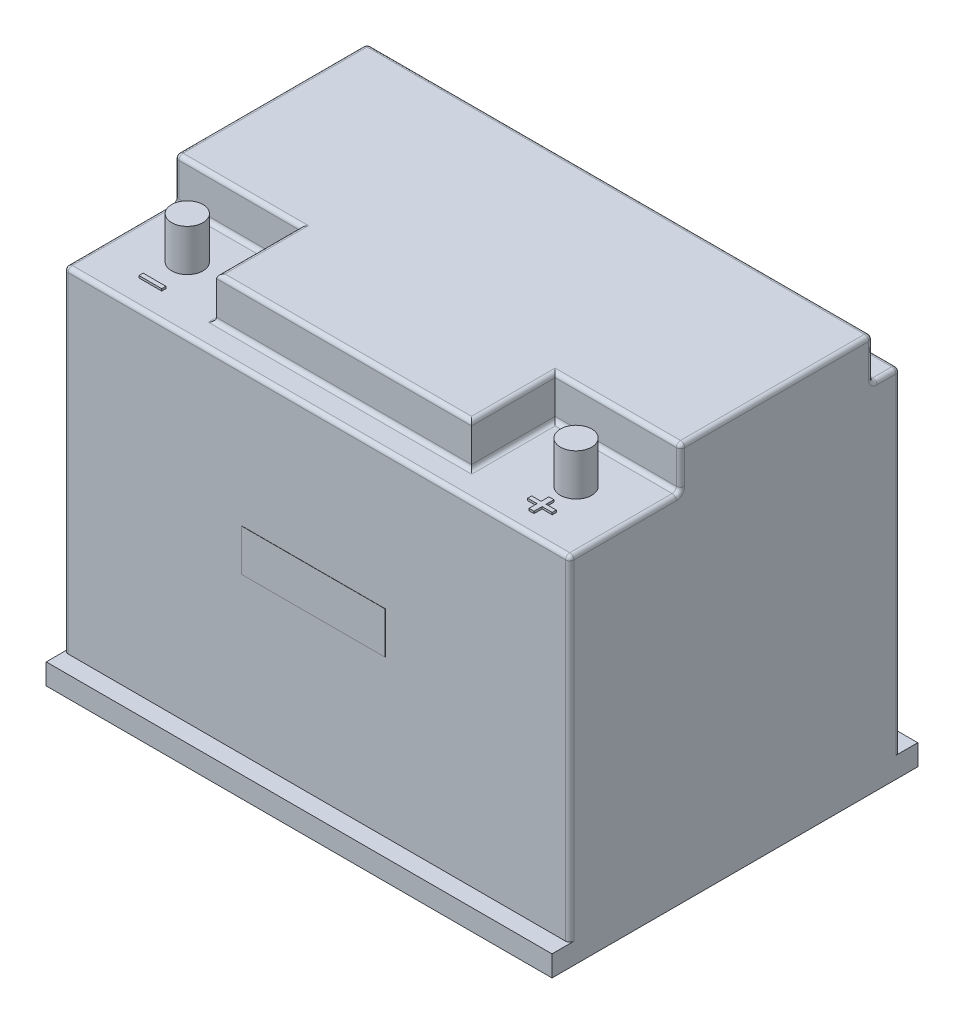
SolidWorks part; units mm, degrees
ref_plane "前视基准面" through (0, 0, 0) normal (0, 0, 1) x (1, 0, 0)
ref_plane "上视基准面" through (0, 0, 0) normal (0, 1, 0) x (1, 0, 0)
ref_plane "右视基准面" through (0, 0, 0) normal (1, 0, 0) x (0, 0, -1)
sketch "草图1" plane through (0, 0, 0) normal (0, 1, 0) x (1, 0, 0)
  line L1 (-121, 87.5) -> (121, 87.5)
  line L2 (-121, 87.5) -> (-121, -87.5)
  line L3 (-121, -87.5) -> (121, -87.5)
  line L4 (121, 87.5) -> (121, -87.5)
  line L5 (-121, 87.5) -> (121, -87.5) construction
  line L6 (-121, -87.5) -> (121, 87.5) construction
  point P0 (0, 0)
  dimension "D1" = 242
  dimension "D2" = 175
extrude "凸台-拉伸1" add sketch "草图1" along normal blind 10
sketch "草图2" plane through (0, 10, 0) normal (0, 1, 0) x (1, 0, 0)
  line L0 (121, -87.5) -> (121, 87.5) construction
  line L1 (-121, 79) -> (121, 79)
  line L2 (-121, 79) -> (-121, -79)
  line L3 (-121, -79) -> (121, -79)
  line L4 (121, 79) -> (121, -79)
  line L5 (-121, 79) -> (121, -79) construction
  line L6 (-121, -79) -> (121, 79) construction
  point P0 (0, 0)
  dimension "D1" = 158
extrude "凸台-拉伸2" add sketch "草图2" along normal blind 160
sketch "草图3" plane through (0, 170, 0) normal (0, 1, 0) x (1, 0, 0)
  line L1 (121, -79) -> (121, 79) construction
  line L2 (-121, 66) -> (121, 66)
  line L3 (-121, 66) -> (-121, -66)
  line L4 (-121, -66) -> (121, -66)
  line L5 (121, 66) -> (121, -66)
  line L6 (-121, 66) -> (121, -66) construction
  line L7 (-121, -66) -> (121, 66) construction
  point P2 (0, 0)
  dimension "D1" = 132
extrude "凸台-拉伸3" add sketch "草图3" along normal blind 20
sketch "草图4" plane through (0, 170, 0) normal (0, 1, 0) x (1, 0, 0)
  line L0 (-121, -66) -> (121, -66) construction
  line L1 (-121, -26) -> (-61, -26)
  line L2 (-121, -26) -> (-121, -66)
  line L3 (-121, -66) -> (-61, -66)
  line L4 (-61, -26) -> (-61, -66)
  line L5 (-121, 66) -> (-121, -66) construction
  line L6 (121, -66) -> (121, 66) construction
  line L7 (61, -26) -> (121, -26)
  line L8 (61, -26) -> (61, -66)
  line L9 (61, -66) -> (121, -66)
  line L10 (121, -26) -> (121, -66)
  dimension "D1" = 60
  dimension "D2" = 40
  dimension "D3" = 0
  dimension "D4" = 60
  dimension "D5" = 40
  dimension "D6" = 0
  dimension "D7" = 0
extrude "切除-拉伸1" cut sketch "草图4" along normal blind 20 contours L3 L4 L1 L2
sketch "草图5" plane through (0, 170, 0) normal (0, 1, 0) x (1, 0, 0)
  line L1 (61, -26) -> (121, -26)
  line L2 (61, -26) -> (61, -66)
  line L3 (61, -66) -> (121, -66)
  line L4 (121, -26) -> (121, -66)
  line L5 (121, 66) -> (-121, 66) construction
  line L6 (-121, 66) -> (-121, -26) construction
  dimension "D1" = 60
  dimension "D2" = 40
  dimension "D3" = 92
  dimension "D4" = 182
extrude "切除-拉伸2" cut sketch "草图5" along normal blind 20 contours L3 L4 L1 L2
fillet "圆角2" radius 2 1 edges
fillet "圆角3" radius 2 1 edges
fillet "圆角4" radius 2 1 edges
fillet "圆角5" radius 2 1 edges
fillet "圆角6" radius 2 8 edges at (-61, 190, 46) (-91, 190, 26) (-121, 190, -20) (0, 190, -66) (121, 190, -20) (91, 190, 26) (61, 190, 46) (0, 190, 66)
fillet "圆角7" radius 2 14 edges at (-121, 179, 26) (121, 179, 26) (120.4142, 189.4142, 25.4142) (-120.4142, 189.4142, 25.4142) (-91, 170, 26) (-61, 170, 46) (61, 170, 46) (91, 170, 26) (0, 170, 79) (-120.4142, 170, 78.4142) (120.4142, 170, 78.4142)
fillet "圆角8" radius 2 10 edges at (120.4142, 189.4142, -65.4142) (-120.4142, 189.4142, -65.4142) (120.4142, 170, -78.4142) (-120.4142, 170, -78.4142) (0, 170, -79)
sketch "草图6" plane through (0, 170, 0) normal (0, 1, 0) x (1, 0, 0)
  line L0 (-63, -28) -> (-119, -28) construction
  line L1 (-63, -68) -> (-63, -28) construction
  circle A0 centre (-93, -48) radius 7.5
  dimension "D1" = 15
  dimension "D2" = 20
  dimension "D3" = 30
extrude "凸台-拉伸4" add sketch "草图6" along normal blind 20
sketch "草图7" plane through (0, 170, 0) normal (0, 1, 0) x (1, 0, 0)
  line L0 (119, -28) -> (63, -28) construction
  line L1 (63, -28) -> (63, -68) construction
  circle A0 centre (93, -48) radius 7.5
  dimension "D1" = 15
  dimension "D2" = 20
  dimension "D3" = 30
extrude "凸台-拉伸5" add sketch "草图7" along normal blind 20 contours A0
sketch "草图9" plane through (0, 170, 0) normal (0, 1, 0) x (1, 0, 0)
  line L0 (-63, -68) -> (-63, -28) construction
  line L1 (-97.9026, -64.2305) -> (-87, -64.2305)
  line L2 (-97.9026, -64.2305) -> (-97.9026, -66.2388)
  line L3 (-97.9026, -66.2388) -> (-87, -66.2388)
  line L4 (-87, -64.2305) -> (-87, -66.2388)
  line L5 (-97.9026, -64.2305) -> (-87, -66.2388) construction
  line L6 (-97.9026, -66.2388) -> (-87, -64.2305) construction
  line L7 (-119, -77) -> (119, -77) construction
  line L8 (-119, -28) -> (-119, -77) construction
  point P0 (-92.4513, -65.2346)
  dimension "D1" = 24
  dimension "D2" = 10.7612
  dimension "D3" = 12.7695
  dimension "D4" = 21.0974
extrude "凸台-拉伸6" add sketch "草图9" along normal blind 1
sketch "草图10" plane through (0, 170, 0) normal (0, 1, 0) x (1, 0, 0)
  line L1 (87.3471, -63.5904) -> (99.1202, -63.5904)
  line L2 (87.3471, -63.5904) -> (87.3471, -65.5311)
  line L3 (87.3471, -65.5311) -> (99.1202, -65.5311)
  line L4 (99.1202, -63.5904) -> (99.1202, -65.5311)
extrude "凸台-拉伸7" add sketch "草图10" along normal blind 1 contours L3 L4 L1 L2
sketch "草图11" plane through (0, 170, 0) normal (0, 1, 0) x (1, 0, 0)
  line L1 (91.8517, -59.8548) -> (94.277, -59.8548)
  line L2 (91.8517, -59.8548) -> (91.8517, -69.389)
  line L3 (91.8517, -69.389) -> (94.277, -69.389)
  line L4 (94.277, -59.8548) -> (94.277, -69.389)
extrude "凸台-拉伸8" add sketch "草图11" along normal blind 1 contours L1 L4 L3 L2
sketch "草图12" plane through (0, 0, 79) normal (0, 0, 1) x (1, 0, 0)
  line L1 (-36.0721, 104.6118) -> (32.7395, 104.6118)
  line L2 (-36.0721, 104.6118) -> (-36.0721, 84.5873)
  line L3 (-36.0721, 84.5873) -> (32.7395, 84.5873)
  line L4 (32.7395, 104.6118) -> (32.7395, 84.5873)
extrude "凸台-拉伸9" add sketch "草图12" along normal blind 0.1 contours L1 L4 L3 L2
